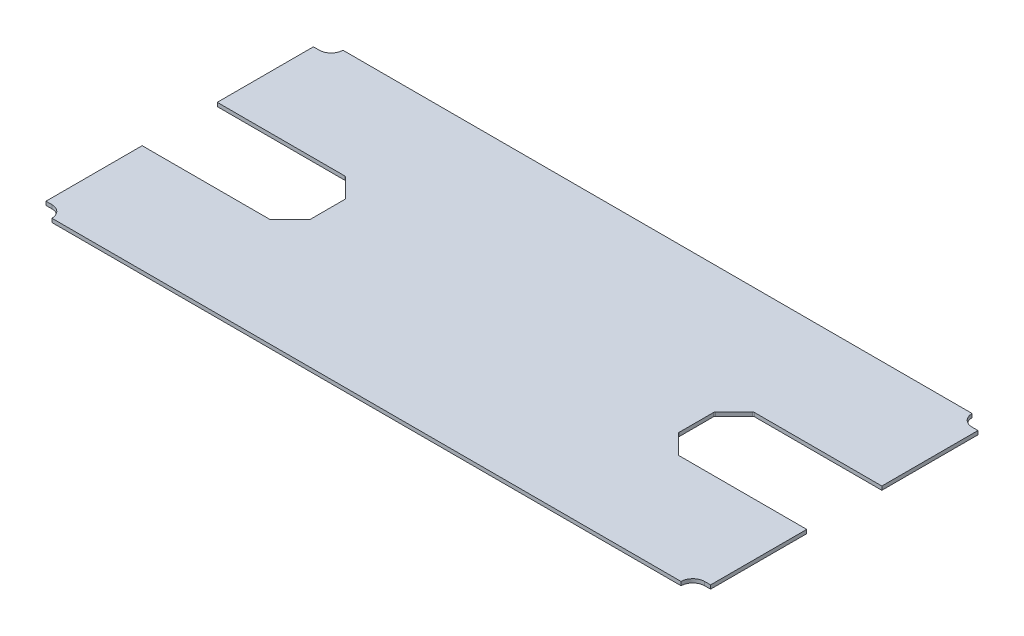
SolidWorks part; units mm, degrees
material "Mahogany"
ref_plane "Front Plane" through (0, 0, 0) normal (0, 0, 1) x (1, 0, 0)
ref_plane "Top Plane" through (0, 0, 0) normal (0, 1, 0) x (1, 0, 0)
ref_plane "Right Plane" through (0, 0, 0) normal (1, 0, 0) x (0, 0, -1)
sketch "Sketch1" plane through (0, 0, 0) normal (0, 1, 0) x (1, 0, 0)
  line L0 (-845, 95.5) -> (-469, 95.5)
  line L1 (-845, 370) -> (845, 370)
  line L2 (-845, 370) -> (-845, -370)
  line L3 (-845, -370) -> (845, -370)
  line L4 (845, 370) -> (845, -370)
  line L5 (-845, 370) -> (845, -370) construction
  line L6 (-845, -370) -> (845, 370) construction
  line L23 (-469, 95.5) -> (-469, -95.5)
  line L24 (-469, -95.5) -> (-845, -95.5)
  line L25 (845, 95.5) -> (469, 95.5)
  line L26 (469, 95.5) -> (469, -95.5)
  line L27 (469, -95.5) -> (845, -95.5)
  line L28 (-845, 340) -> (-830, 340)
  line L29 (0, -370) -> (0, 370) construction
  line L30 (-845, 0) -> (845, 0) construction
  line L31 (-845, -340) -> (-830, -340)
  line L32 (845, 340) -> (830, 340)
  line L33 (845, -340) -> (830, -340)
  arc A0 (-830, 340) -> (-800, 370) centre (-830, 370) ccw
  arc A1 (-830, -340) -> (-800, -370) centre (-830, -370) cw
  arc A2 (830, 340) -> (800, 370) centre (830, 370) cw
  arc A3 (830, -340) -> (800, -370) centre (830, -370) ccw
  point P0 (0, 0)
  point P26 (469, 0)
  point P27 (-469, 0)
  dimension "D6" = 30
  dimension "D4" = 376
  dimension "D5" = 191
  dimension "D2" = 740
  dimension "D1" = 1690
  dimension "D3" = 15
extrude "Boss-Extrude1" add sketch "Sketch1" along normal blind 9.525 contours L27 L26 L25 L4 L1 L2 L0 L23 L24 L3 region at (0, 0, 0)
chamfer "Chamfer1" distance 50 angle 45 4 edges at (469, 4.7625, 95.5) (469, 4.7625, -95.5) (-469, 4.7625, 95.5) (-469, 4.7625, -95.5)
fillet "Fillet2" radius 5 8 edges at (469, 4.7625, -45.5) (469, 4.7625, 45.5) (519, 4.7625, 95.5) (519, 4.7625, -95.5) (-519, 4.7625, 95.5) (-469, 4.7625, 45.5) (-469, 4.7625, -45.5) (-519, 4.7625, -95.5)
equation "\"W\"= 1700"
equation "\"L\"= 780"
equation "\"H\"= 780"
equation "\"ARM_BOLT_SPACING\"= 166"
equation "\"ARM_TO_WALL\"= 200"
equation "\"D4@Sketch1\"=\"ARM_TO_WALL\"+\"ARM_BOLT_SPACING\"+10"
equation "\"D5@Sketch1\"=\"ARM_BOLT_SPACING\"+25"
equation "\"D2@Sketch1\"=\"L\"-40"
equation "\"D1@Sketch1\"=\"W\"-10"
